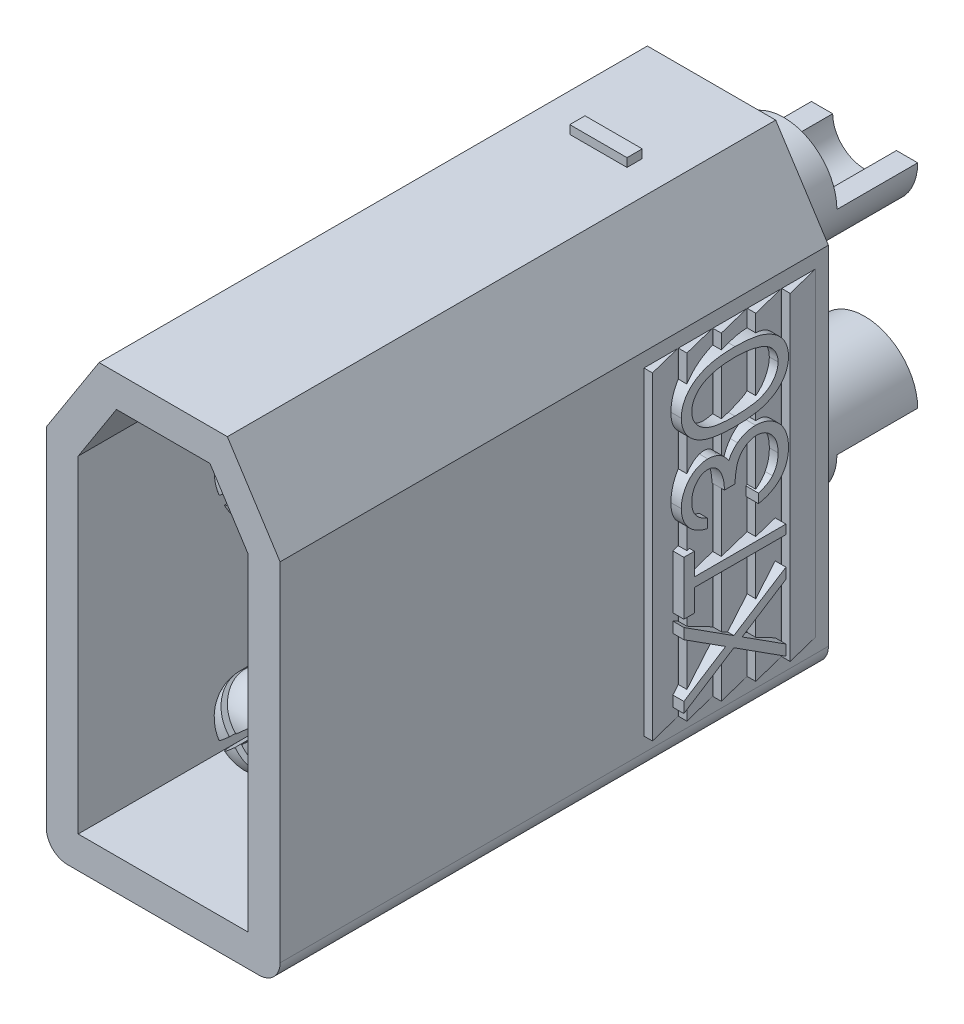
SolidWorks part; units mm, degrees
ref_plane "Front Plane" through (0, 0, 0) normal (0, 0, 1) x (1, 0, 0)
ref_plane "Top Plane" through (0, 0, 0) normal (0, 1, 0) x (1, 0, 0)
ref_plane "Right Plane" through (0, 0, 0) normal (1, 0, 0) x (0, 0, -1)
sketch "Sketch3" plane through (0, 0, 0) normal (0, 0, 1) x (1, 0, 0)
  line L0 (0, 0.9104) -> (0, 10.0104) construction
  line L1 (0, 5.4604) -> (-2, 5.4604) construction
  line L2 (0, 5.4604) -> (2, 5.4604) construction
  line L3 (0, 10.0104) -> (-1.1, 10.0104) construction
  line L4 (-1.1, 10.0104) -> (-1.1, 8.6104) construction
  line L5 (2, 0.9104) -> (-2, 0.9104)
  line L6 (-2, 0.9104) -> (-2, 8.6104)
  line L7 (-2, 8.6104) -> (-1.1, 10.0104)
  line L8 (-1.1, 10.0104) -> (1.1, 10.0104)
  line L9 (2, 0.9104) -> (2, 8.6104)
  line L10 (2, 8.6104) -> (1.1, 10.0104)
  line L11 (2.25, 0.1604) -> (-2.25, 0.1604)
  line L12 (-2.75, 0.6604) -> (-2.75, 8.8306)
  line L13 (-2.75, 8.8306) -> (-1.5095, 10.7604)
  line L14 (-1.5095, 10.7604) -> (1.5095, 10.7604)
  line L15 (2.75, 8.8306) -> (1.5095, 10.7604)
  line L16 (2.75, 0.6604) -> (2.75, 8.8306)
  line L17 (2.75, 0.1604) -> (-2.75, 0.1604) construction
  line L18 (2.75, 0.1604) -> (2.75, 8.8306) construction
  line L19 (-2.75, 0.1604) -> (-2.75, 8.8306) construction
  arc A0 (2.25, 0.1604) -> (2.75, 0.6604) centre (2.25, 0.6604) ccw
  arc A1 (-2.25, 0.1604) -> (-2.75, 0.6604) centre (-2.25, 0.6604) cw
  point P22 (2.75, 0.1604)
  dimension "D9" = 0.5
  dimension "D1" = 9.1
  dimension "D2" = 2
  dimension "D3" = 2
  dimension "D4" = 1.1
  dimension "D5" = 1.4
  dimension "D8" = 10.6
  dimension "D6" = 0.75
extrude "Boss-Extrude2" add sketch "Sketch3" along normal blind 12.9
sketch "Sketch4" plane through (0, 0, 0) normal (0, 0, 1) x (1, 0, 0)
  line L6 (-1.5, 10.0104) -> (1.5, 10.0104)
  line L7 (-2, 9.5104) -> (-2, 0.9104)
  line L8 (-2, 0.9104) -> (2, 0.9104)
  line L9 (2, 9.5104) -> (2, 0.9104)
  arc A0 (1.5, 10.0104) -> (2, 9.5104) centre (1.5, 9.5104) cw
  arc A1 (-1.5, 10.0104) -> (-2, 9.5104) centre (-1.5, 9.5104) ccw
  dimension "D1" = 0.5
extrude "Boss-Extrude3" add sketch "Sketch4" along normal blind 3.55 from offset 1.45
sketch "Sketch6" plane through (0, 0, 0) normal (0, 1, 0) x (1, 0, 0)
  line L0 (2.75, -0.3) -> (2.75, -1.1)
  line L1 (2.75, -12.9) -> (2.75, 0) construction
  line L2 (2.75, -1.1) -> (2.95, -1.1)
  line L3 (2.75, 0) -> (1.5095, 0) construction
  line L4 (0, 0) -> (0, -2.7855) construction
  line L5 (2.95, -1.1) -> (2.75, -0.3)
  line L6 (2.75, -1.11) -> (2.75, -1.91)
  line L7 (2.75, -1.91) -> (2.95, -1.91)
  line L8 (2.95, -1.91) -> (2.75, -1.11)
  line L9 (2.75, -1.92) -> (2.75, -2.72)
  line L10 (2.75, -2.72) -> (2.95, -2.72)
  line L11 (2.95, -2.72) -> (2.75, -1.92)
  line L12 (2.75, -2.73) -> (2.75, -3.53)
  line L13 (2.75, -3.53) -> (2.95, -3.53)
  line L14 (2.95, -3.53) -> (2.75, -2.73)
  line L15 (2.75, -3.54) -> (2.75, -4.34)
  line L16 (2.75, -4.34) -> (2.95, -4.34)
  line L17 (2.95, -4.34) -> (2.75, -3.54)
  line L18 (-2.95, -4.34) -> (-2.75, -3.54)
  line L19 (-2.75, -4.34) -> (-2.95, -4.34)
  line L20 (-2.75, -3.54) -> (-2.75, -4.34)
  line L21 (-2.95, -3.53) -> (-2.75, -2.73)
  line L22 (-2.75, -3.53) -> (-2.95, -3.53)
  line L23 (-2.75, -2.73) -> (-2.75, -3.53)
  line L24 (-2.95, -2.72) -> (-2.75, -1.92)
  line L25 (-2.75, -2.72) -> (-2.95, -2.72)
  line L26 (-2.75, -1.92) -> (-2.75, -2.72)
  line L27 (-2.95, -1.91) -> (-2.75, -1.11)
  line L28 (-2.75, -1.91) -> (-2.95, -1.91)
  line L29 (-2.75, -1.11) -> (-2.75, -1.91)
  line L30 (-2.95, -1.1) -> (-2.75, -0.3)
  line L31 (-2.75, -1.1) -> (-2.95, -1.1)
  line L32 (-2.75, -0.3) -> (-2.75, -1.1)
  dimension "D1" = 0.3
  dimension "D2" = 0.8
  dimension "D3" = 5
extrude "Boss-Extrude4" add sketch "Sketch6" along normal blind 7.5 from offset 1
sketch "Sketch7" plane through (0, 0, 0) normal (0, 0, 1) x (1, 0, 0)
  line L0 (-2, 0.9104) -> (2, 0.9104) construction
  line L1 (1.1, 10.0104) -> (-1.1, 10.0104) construction
  circle A0 centre (0, 2.9604) radius 1.25
  circle A1 centre (0, 7.9604) radius 1.25
  dimension "D1" = 2.5
  dimension "D2" = 2.5
  dimension "D3" = 5
  dimension "D4" = 2.05
  dimension "D5" = 2.05
extrude "Boss-Extrude5" add sketch "Sketch7" along normal up to surface (5 mm away) and the other way blind 3.6 separate body up to face at (0, 6.5104, 5)
sketch "Sketch8" plane through (0, 0, -3.6) normal (0, 0, -1) x (-1, 0, 0)
  circle A1 centre (0, 2.9604) radius 0.75
  circle A2 centre (0, 7.9604) radius 0.75
extrude "Cut-Extrude1" cut sketch "Sketch8" against normal blind 3
sketch "Sketch9" plane through (0, 0, 0) normal (1, 0, 0) x (0, 0, -1)
  line L0 (3.6, 6.7104) -> (3.6, 9.2104) construction
  line L1 (3.6, 7.9604) -> (1.7, 7.9604)
  line L2 (3.6, 7.9604) -> (3.6, 9.2104)
  line L3 (3.6, 9.2104) -> (1.7, 9.2104)
  line L4 (1.7, 7.9604) -> (1.7, 9.2104)
  line L5 (3.6, 9.2104) -> (-5, 9.2104) construction
  line L6 (3.6, 1.7104) -> (3.6, 4.2104) construction
  line L7 (3.6, 2.9604) -> (1.7, 2.9604)
  line L8 (3.6, 2.9604) -> (3.6, 1.7104)
  line L9 (3.6, 1.7104) -> (1.7, 1.7104)
  line L10 (1.7, 2.9604) -> (1.7, 1.7104)
  line L11 (-5, 1.7104) -> (3.6, 1.7104) construction
  dimension "D1" = 1.9
extrude "Cut-Extrude2" cut sketch "Sketch9" against normal through all and the other way through all
chamfer "Chamfer1" distance 0.75 angle 45 1 edges at (-0.75, 7.9604, -0.6)
chamfer "Chamfer3" distance 0.75 angle 45 1 edges at (-0.75, 2.9604, -0.6)
sketch "Sketch10" plane through (0, 0, 5) normal (0, 0, 1) x (1, 0, 0)
  circle A0 centre (0, 7.9604) radius 0.97
  circle A1 centre (0, 2.9604) radius 0.97
extrude "Boss-Extrude6" add sketch "Sketch10" along normal blind 6.2 separate body
fillet "Fillet1" radius 0.8 1 edges at (0.97, 7.9604, 11.2)
fillet "Fillet2" radius 0.8 1 edges at (0.97, 2.9604, 11.2)
sketch "Sketch11" plane through (0, 0, 11.2) normal (0, 0, 1) x (1, 0, 0)
  line L0 (-0.7089, 2.2066) -> (0.8407, 3.5636) construction
  line L1 (-0.7089, 2.2066) -> (-0.8407, 2.3571) construction
  line L2 (0.8407, 3.5636) -> (0.7089, 3.7141) construction
  line L3 (-0.8407, 2.3571) -> (0.7089, 3.7141) construction
  line L4 (-0.7089, 2.2066) -> (0.7089, 3.7141) construction
  line L5 (0.8407, 3.5636) -> (-0.8407, 2.3571) construction
  line L6 (-0.7537, 3.6693) -> (0.6033, 2.1197) construction
  line L7 (0.6033, 2.1197) -> (0.7537, 2.2514) construction
  line L8 (-0.6033, 3.8011) -> (0.7537, 2.2514) construction
  line L9 (-0.7537, 3.6693) -> (-0.6033, 3.8011) construction
  line L10 (-0.6033, 3.8011) -> (0.0094, 3.1015)
  line L11 (0.0094, 3.1015) -> (0.7089, 3.7141)
  line L12 (0.7089, 3.7141) -> (0.8407, 3.5636)
  line L13 (0.8407, 3.5636) -> (0.1411, 2.951)
  line L14 (0.1411, 2.951) -> (0.7537, 2.2514)
  line L15 (0.7537, 2.2514) -> (0.6033, 2.1197)
  line L16 (0.6033, 2.1197) -> (-0.0094, 2.8193)
  line L17 (-0.0094, 2.8193) -> (-0.7089, 2.2066)
  line L18 (-0.7089, 2.2066) -> (-0.8407, 2.3571)
  line L19 (-0.8407, 2.3571) -> (-0.1411, 2.9697)
  line L20 (-0.1411, 2.9697) -> (-0.7537, 3.6693)
  line L21 (-0.7537, 3.6693) -> (-0.6033, 3.8011)
  line L22 (-0.8407, 7.3571) -> (-0.1411, 7.9697)
  line L23 (-0.1411, 7.9697) -> (-0.7537, 8.6693)
  line L24 (-0.7537, 8.6693) -> (0.6033, 7.1197) construction
  line L25 (0.1411, 7.951) -> (0.7537, 7.2514)
  line L26 (-0.7089, 7.2066) -> (-0.8407, 7.3571) construction
  line L27 (-0.6033, 8.8011) -> (0.0094, 8.1015)
  line L28 (0.8407, 8.5636) -> (0.7089, 8.7141) construction
  line L29 (0.8407, 8.5636) -> (0.1411, 7.951)
  line L30 (0.8407, 8.5636) -> (-0.8407, 7.3571) construction
  line L31 (0.7089, 8.7141) -> (0.8407, 8.5636)
  line L32 (-0.0094, 7.8193) -> (-0.7089, 7.2066)
  line L33 (-0.7537, 8.6693) -> (-0.6033, 8.8011) construction
  line L34 (-0.7089, 7.2066) -> (-0.8407, 7.3571)
  line L35 (-0.7537, 8.6693) -> (-0.6033, 8.8011)
  line L36 (-0.7089, 7.2066) -> (0.8407, 8.5636) construction
  line L37 (-0.6033, 8.8011) -> (0.7537, 7.2514) construction
  line L38 (-0.8407, 7.3571) -> (0.7089, 8.7141) construction
  line L39 (0.0094, 8.1015) -> (0.7089, 8.7141)
  line L40 (-0.7089, 7.2066) -> (0.7089, 8.7141) construction
  line L41 (0.7537, 7.2514) -> (0.6033, 7.1197)
  line L42 (0.6033, 7.1197) -> (0.7537, 7.2514) construction
  line L43 (0.6033, 7.1197) -> (-0.0094, 7.8193)
  point P1 (0, 2.9604)
  point P14 (0, 7.9604)
  dimension "D1" = 0.2
  dimension "D2" = 0.2
extrude "Cut-Extrude3" cut sketch "Sketch11" against normal blind 3.1
sketch "Sketch12" plane through (0, 0.1604, 0) normal (0, -1, 0) x (1, 0, 0)
  line L0 (0, 0) -> (0, 1) construction
  line L1 (0, 1) -> (-1.45, 1) construction
  line L2 (-1.45, 1) -> (0.8, 1) construction
  text T0 "+\r\n"
  point P3 (0, 0)
  dimension "D1" = 1
  dimension "D2" = 1.45
extrude "Boss-Extrude7" add sketch "Sketch12" along normal blind 0.2
sketch "Sketch13" plane through (0, 10.7604, 0) normal (0, 1, 0) x (-1, 0, 0)
  line L0 (0.2478, 0.1887) -> (0.2478, 1.1887) construction
  line L1 (0.2478, 1.1887) -> (-1.1522, 1.1887) construction
  line L2 (-1.1522, 1.1887) -> (1.0478, 1.1887) construction
  text T0 "-\r\n"
  point P3 (0.2478, 0.1887)
  dimension "D1" = 1
  dimension "D2" = 1.4
extrude "Boss-Extrude8" add sketch "Sketch13" along normal blind 0.2
sketch "Sketch14" plane through (-2.75, 0, 0) normal (-1, 0, 0) x (0, 0, 1)
  line L0 (0.3, 4.75) -> (1.3, 4.75) construction
  line L1 (0.3, 8.5) -> (0.3, 1) construction
  line L2 (1.3, 4.75) -> (1.3, 8.35) construction
  line L3 (1.3, 8.35) -> (1.3, 1.15) construction
  text T0 "XT30\r\n" font "Century Gothic" height 2.4
  dimension "D1" = 1
  dimension "D2" = 3.6
  dimension "D3" = 7.2
extrude "Boss-Extrude9" add sketch "Sketch14" along normal blind 0.3
sketch "Sketch15" plane through (2.75, 0, 0) normal (1, 0, 0) x (0, 0, -1)
  line L0 (-0.3, 4.75) -> (-1.3, 4.75) construction
  line L2 (-1.3, 4.75) -> (-1.3, 1.15) construction
  line L3 (-1.3, 1.15) -> (-1.3, 8.35) construction
  text T0 "XT30\r\n" font "Century Gothic" height 2.4
  dimension "D1" = 1
  dimension "D2" = 3.6
  dimension "D3" = 7.2
extrude "Boss-Extrude10" add sketch "Sketch15" along normal blind 0.3
